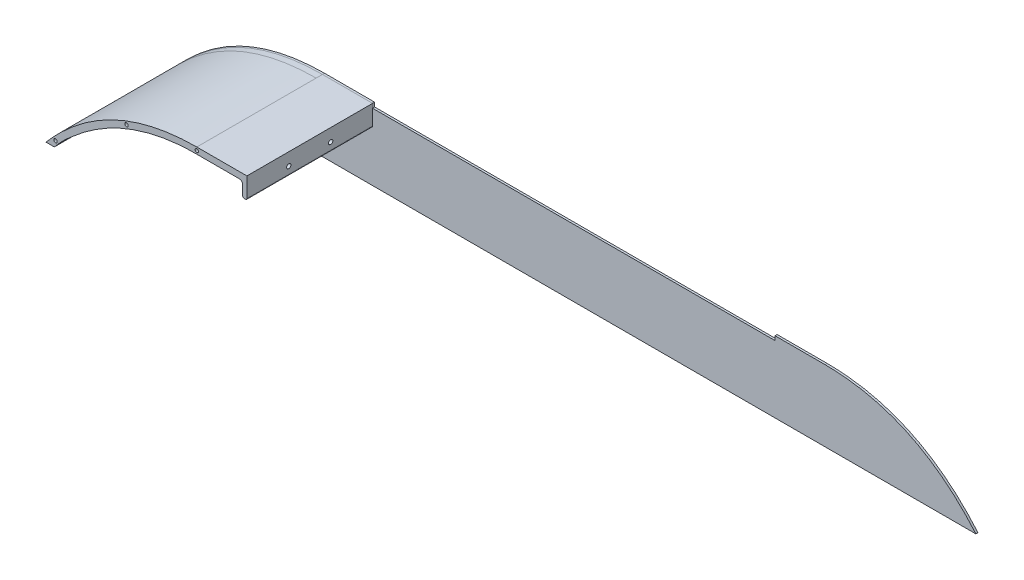
SolidWorks part; units mm, degrees
ref_plane "Front Plane" through (0, 0, 0) normal (0, 0, 1) x (1, 0, 0)
ref_plane "Top Plane" through (0, 0, 0) normal (0, 1, 0) x (1, 0, 0)
ref_plane "Right Plane" through (0, 0, 0) normal (1, 0, 0) x (0, 0, -1)
sketch "Sketch1" plane through (0, 0, 0) normal (0, 0, 1) x (1, 0, 0)
  line L0 (0, 0) -> (-304.8, 0)
  line L1 (0, 0) -> (609.6, 0)
  line L2 (0, 0) -> (0, 107.95) construction
  line L3 (0, 107.95) -> (609.6, 107.95)
  line L4 (609.6, 0) -> (609.6, 107.95) construction
  line L5 (609.6, 0) -> (914.4, 0)
  line L6 (304.8, -1000) -> (304.8, 49000) construction
  line L7 (0, 107.95) -> (-76.2, 107.95)
  line L8 (609.6, 107.95) -> (685.8, 107.95)
  spline S0 degree 2 poles (-304.8, 0) (-213.404, 107.36) (-76.2, 107.95) knots 0 0 0 1 1 1
  spline S1 degree 2 poles (914.4, 0) (823.004, 107.36) (685.8, 107.95) knots 0 0 0 1 1 1
  point P11 (304.8, 0)
  dimension "D1" = 609.6
  dimension "D2" = 107.95
  dimension "D3" = 304.8
  dimension "D4" = 76.2
extrude "Boss-Extrude1" add sketch "Sketch1" along normal blind 3.175
sketch "Sketch2" plane through (0, 0, 3.175) normal (0, 0, 1) x (1, 0, 0)
  line L8 (685.8, 107.95) -> (-76.2, 107.95) construction
  line L11 (0, 107.95) -> (609.6, 107.95)
  line L12 (0, 107.95) -> (0, 101.6) construction
  line L13 (0, 101.6) -> (609.6, 101.6)
  line L14 (609.6, 107.95) -> (609.6, 101.6) construction
  line L15 (-0.254, 107.95) -> (-0.254, 101.6)
  line L16 (609.854, 107.95) -> (609.854, 101.6)
  line L19 (609.6, 107.95) -> (609.854, 107.95)
  line L20 (609.6, 101.6) -> (609.854, 101.6)
  line L21 (-0.254, 107.95) -> (0, 107.95)
  line L22 (-0.254, 101.6) -> (0, 101.6)
  dimension "D1" = 609.6
  dimension "D2" = 6.35
  dimension "D3" = 0.254
  dimension "D4" = 0.254
extrude "Cut-Extrude1" cut sketch "Sketch2" against normal through all
sketch "Sketch3" plane through (0, 0, 3.175) normal (0, 0, 1) x (1, 0, 0)
  line L5 (-76.0908, 82.5502) -> (-76.2, 107.95) construction
  line L6 (685.8, 107.95) -> (609.854, 107.95)
  line L7 (609.854, 107.95) -> (609.854, 101.6)
  line L8 (609.854, 101.6) -> (-0.254, 101.6)
  line L9 (-0.254, 101.6) -> (-0.254, 107.95)
  line L10 (-0.254, 107.95) -> (-76.2, 107.95)
  line L11 (-304.8, 0) -> (914.4, 0)
  line L19 (-304.8, 0) -> (-254.508, 0)
  line L20 (-304.8, 0) -> (914.4, 0) construction
  line L21 (-254.508, 0) -> (-254.508, 15.3448)
  line L22 (-76.2, 107.95) -> (-0.254, 107.95)
  line L23 (-0.254, 107.95) -> (-0.254, 76.2)
  line L24 (-0.254, 76.2) -> (-6.604, 76.2)
  line L25 (-6.604, 76.2) -> (-6.604, 82.5502)
  line L26 (-6.604, 82.5502) -> (-76.0908, 82.5502)
  parabola Q2 (-76.2, 107.95) -> (-304.8, 0) focus (-138.8032, -41.5009) apex (-192.9562, 84.7198)
  parabola Q3 (914.4, 0) -> (685.8, 107.95) focus (748.4032, -41.5009) apex (802.5562, 84.7198)
  parabola Q4 (-76.2, 107.95) -> (-304.8, 0) focus (-138.8032, -41.5009) apex (-192.9562, 84.7198)
  spline S0 degree 1 poles (-76.0908, 82.5502) (-285.4592, -16.4649) knots 0 0 1 1 construction
  spline S1 degree 3 poles (-76.0908, 82.5502) (-78.7263, 82.5389) (-84.0207, 82.4515) (-94.414, 82.0204) (-107.175, 81.0024) (-122.0857, 79.0209) (-140.2937, 75.5918) (-157.8592, 70.8643) (-175.9104, 64.4537) (-194.5198, 56.4637) (-212.4049, 46.7322) (-228.6865, 35.996) (-240.414, 27.3) (-249.9299, 19.4397) (-257.5609, 12.6326) (-263.3873, 7.1473) (-268.2089, 2.3627) (-271.8925, -1.4301) (-275.5622, -5.3024) (-280.0978, -10.2646) (-283.6939, -14.3913) (-285.4592, -16.4649) knots 0.497516 0.497516 0.497516 0.497516 0.497684 0.497853 0.498189 0.498526 0.498863 0.499456 0.499793 0.50021 0.500884 0.501221 0.501558 0.501878 0.502046 0.502231 0.502399 0.502483 0.502568 0.502737 0.502905 0.502905 0.502905 0.502905 only from (-76.0908, 82.5502) to (-270.5007, 0) construction
  spline S2 degree 2 poles (-254.508, 15.3448) (-177.7983, 82.8932) (-76.0908, 82.5502) knots 0 0 0 1 1 1
  dimension "D2" = 31.75
  dimension "D3" = 6.35
  dimension "D5" = 50.292
  dimension "D1" = 0
  dimension "D4" = 25.4
extrude "Boss-Extrude2" add sketch "Sketch3" along normal blind 9.525
sketch "Sketch5" plane through (0, 0, 12.7) normal (0, 0, 1) x (1, 0, 0)
  line L7 (-304.8, 0) -> (-292.1, 0)
  line L8 (-76.0372, 98.4251) -> (-6.604, 98.4251)
  line L9 (-6.604, 98.4251) -> (-6.604, 82.5502)
  line L14 (-304.8, 0) -> (-254.508, 0)
  line L15 (-254.508, 0) -> (-254.508, 15.3448)
  line L16 (-76.0908, 82.5502) -> (-6.604, 82.5502)
  line L17 (-6.604, 82.5502) -> (-6.604, 76.2)
  line L18 (-6.604, 76.2) -> (-0.254, 76.2)
  line L19 (-0.254, 76.2) -> (-0.254, 107.95)
  line L20 (-0.254, 107.95) -> (-76.2, 107.95)
  line L24 (-6.604, 82.5502) -> (-6.604, 76.2)
  line L25 (-6.604, 76.2) -> (-0.254, 76.2)
  line L26 (-0.254, 76.2) -> (-0.254, 107.95)
  line L27 (-0.254, 107.95) -> (-76.2, 107.95)
  parabola Q4 (-76.2, 107.95) -> (-304.8, 0) focus (-138.8032, -41.5009) apex (-192.9562, 84.7198)
  parabola Q5 (-254.508, 15.3448) -> (-76.0908, 82.5502) focus (-126.3995, -51.2914) apex (-169.7975, 66.5726)
  parabola Q6 (-76.2, 107.95) -> (-304.8, 0) focus (-138.8032, -41.5009) apex (-192.9562, 84.7198)
  parabola Q7 (-254.508, 15.3448) -> (-76.0908, 82.5502) focus (-126.3995, -51.2914) apex (-169.7975, 66.5726) construction
  spline S0 degree 1 poles (-264.9993, 27.259) (-76.0372, 98.4251) knots 0 0 1 1 construction
  spline S1 degree 3 poles (-264.9993, 27.259) (-263.3249, 28.7335) (-259.9376, 31.6547) (-253.107, 37.2998) (-244.419, 44.0244) (-233.7687, 51.5472) (-219.2659, 60.8476) (-200.5783, 71.0931) (-177.2837, 81.1523) (-153.1553, 88.9561) (-132.3866, 93.5719) (-115.3933, 96.1333) (-102.4647, 97.4901) (-91.5371, 98.1519) (-82.7134, 98.4012) (-78.2591, 98.4326) (-76.0372, 98.4251) knots 0.497832 0.497832 0.497832 0.497832 0.497965 0.498098 0.498363 0.498629 0.498895 0.499427 0.499958 0.50049 0.501022 0.501287 0.501553 0.501819 0.501952 0.502085 0.502085 0.502085 0.502085
  spline S2 degree 2 poles (-264.9993, 27.259) (-280.0432, 15.0907) (-292.1, 0) knots 0 0 0 1 1 1
  dimension "D3" = 12.7
  dimension "D1" = 0
  dimension "D2" = 15.875
extrude "Boss-Extrude3" add sketch "Sketch5" along normal blind 180.975
sketch "Sketch6" plane through (0, 0, 12.7) normal (0, 0, 1) x (1, 0, 0)
  line L1 (-254.508, 0) -> (-226.4253, 0)
  line L2 (-254.508, 0) -> (-254.508, 28.575)
  line L3 (-254.508, 28.575) -> (-226.4253, 28.575)
  line L4 (-226.4253, 0) -> (-226.4253, 28.575)
  dimension "D1" = 28.575
extrude "Cut-Extrude2" cut sketch "Sketch6" against normal up to surface (9.525 mm away) up to face at (204.1979, 60.3971, 3.175)
sketch "Sketch7" plane through (0, 0, 12.7) normal (0, 0, 1) x (1, 0, 0)
  line L0 (-292.1, 0) -> (-254.508, 0) construction
  line L1 (-254.508, 0) -> (-254.508, 28.575) construction
  line L2 (-76.0651, 90.1702) -> (-9.6958, 90.1702) construction
  line L3 (-6.604, 98.4251) -> (-6.604, 76.2) construction
  circle A0 centre (-267.208, 10.16) radius 3.275
  circle A1 centre (-175.3658, 72.6223) radius 3.275
  circle A3 centre (-57.404, 90.1702) radius 3.275
  parabola Q0 (-238.3942, 28.575) -> (-76.0908, 82.5502) focus (-126.3995, -51.2914) apex (-169.7975, 66.5726) construction
  parabola Q1 (-238.3942, 28.575) -> (-76.0908, 82.5502) focus (-126.3995, -51.2914) apex (-169.7975, 66.5726) construction
  spline S0 degree 1 poles (-243.0182, 34.6317) (-76.0651, 90.1702) knots 0 0 1 1 construction
  spline S1 degree 3 poles (-243.0182, 34.6317) (-239.9935, 36.9409) (-233.8311, 41.4586) (-224.4638, 47.7679) (-214.9157, 53.6525) (-202.0674, 60.8581) (-190.551, 66.4075) (-178.8009, 71.3309) (-171.8366, 73.9914) (-159.5844, 78.2202) (-143.5556, 82.8056) (-125.3458, 86.3973) (-110.4698, 88.391) (-99.1613, 89.4468) (-89.6088, 89.961) (-81.8979, 90.1535) (-78.0064, 90.1767) (-76.0651, 90.1702) knots 0.498271 0.498271 0.498271 0.498271 0.49851 0.498748 0.498986 0.499225 0.499694 0.499813 0.500051 0.500178 0.500655 0.501131 0.50137 0.501608 0.501846 0.501966 0.502085 0.502085 0.502085 0.502085 construction
  dimension "D1" = 6.55
  dimension "D5" = 6.55
  dimension "D6" = 6.55
  dimension "D2" = 10.16
  dimension "D4" = 12.7
  dimension "D7" = 50.8
  dimension "D3" = 7.62
extrude "Cut-Extrude3" cut sketch "Sketch7" against normal through all
sketch "Sketch8" plane through (-0.254, 0, 0) normal (1, 0, 0) x (0, 0, -1)
  line L0 (-1151.3542, 88.9) -> (48848.6458, 88.9) construction
  line L1 (-193.675, 76.2) -> (-3.175, 76.2) construction
  line L2 (-3.175, 76.2) -> (-3.175, 101.6) construction
  circle A2 centre (-66.675, 88.9) radius 3.275
  circle A5 centre (-130.175, 88.9) radius 3.275
  dimension "D2" = 6.55
  dimension "D4" = 63.5
  dimension "D1" = 12.7
  dimension "D3" = 2
extrude "Cut-Extrude5" cut sketch "Sketch8" against normal up to surface (6.35 mm away) up to face at (-6.604, 85.7251, 69.85)
sketch "Sketch9" plane through (0, 0, 193.675) normal (0, 0, 1) x (1, 0, 0)
  circle A0 centre (-290.3708, 9.1426) radius 2.6
  circle A1 centre (-182.7594, 83.8165) radius 2.6
  circle A2 centre (-76.1798, 103.25) radius 2.6
  parabola Q0 (-76.2, 107.95) -> (-304.8, 0) focus (-138.8032, -41.5009) apex (-192.9562, 84.7198) construction
  parabola Q1 (-76.2, 107.95) -> (-304.8, 0) focus (-138.8032, -41.5009) apex (-192.9562, 84.7198) construction
  spline S0 degree 1 poles (-76.1798, 103.25) (-301.2212, -3.0467) knots 0 0 1 1 construction
  spline S1 degree 3 poles (-76.1798, 103.25) (-78.9851, 103.238) (-84.6167, 103.1451) (-95.7036, 102.6853) (-109.3519, 101.5971) (-125.3575, 99.4709) (-145.1456, 95.7451) (-161.7727, 91.2541) (-177.9517, 85.7316) (-188.5878, 81.5829) (-206.0869, 73.7491) (-227.5653, 62.0602) (-249.2337, 46.8941) (-265.8815, 33.1047) (-277.7275, 22.2059) (-286.3, 13.5161) (-292.1052, 7.2837) (-296.2196, 2.7435) (-299.3516, -0.8505) (-301.2212, -3.0467) knots 0.497516 0.497516 0.497516 0.497516 0.497684 0.497853 0.498189 0.498526 0.498863 0.499468 0.499636 0.499973 0.50021 0.500884 0.501558 0.501895 0.502231 0.502544 0.502628 0.502737 0.502905 0.502905 0.502905 0.502905 construction
  dimension "D2" = 5.2
  dimension "D3" = 5.2
  dimension "D4" = 5.2
  dimension "D1" = 4.7
extrude "Cut-Extrude6" cut sketch "Sketch9" against normal blind 12.7
sketch "Sketch11" plane through (-254.508, 0, 0) normal (1, 0, 0) x (0, 0, -1)
  line L0 (-3.175, 0) -> (-3.175, 28.575) construction
  line L1 (-12.7, 0) -> (-3.175, 0) construction
  circle A0 centre (-7.1374, 3.9751) radius 1.9
  circle A3 centre (-7.1374, 21.4251) radius 1.9
  dimension "D3" = 3.8
  dimension "D1" = 3.9624
  dimension "D2" = 3.9751
  dimension "D4" = 2
extrude "Boss-Extrude5" add sketch "Sketch11" along normal blind 9.525
fillet "Fillet1" radius 5 1 edges at (-6.604, 98.4251, 103.1875)
fillet "Fillet2" radius 2 2 edges at (-238.3942, 28.575, 7.9375) (-254.508, 28.575, 7.9375)
fillet "Fillet3" radius 1 1 edges at (-292.1, 0, 103.1875)
fillet "Fillet5" radius 2 3 edges at (-0.254, 76.2, 98.425) (-6.604, 76.2, 98.425) (-6.604, 82.5502, 7.9375)
split "Split1" bodies to split 110 resulting bodies 113 114 split by face at (88.8021, 59.1412, 3.175)
